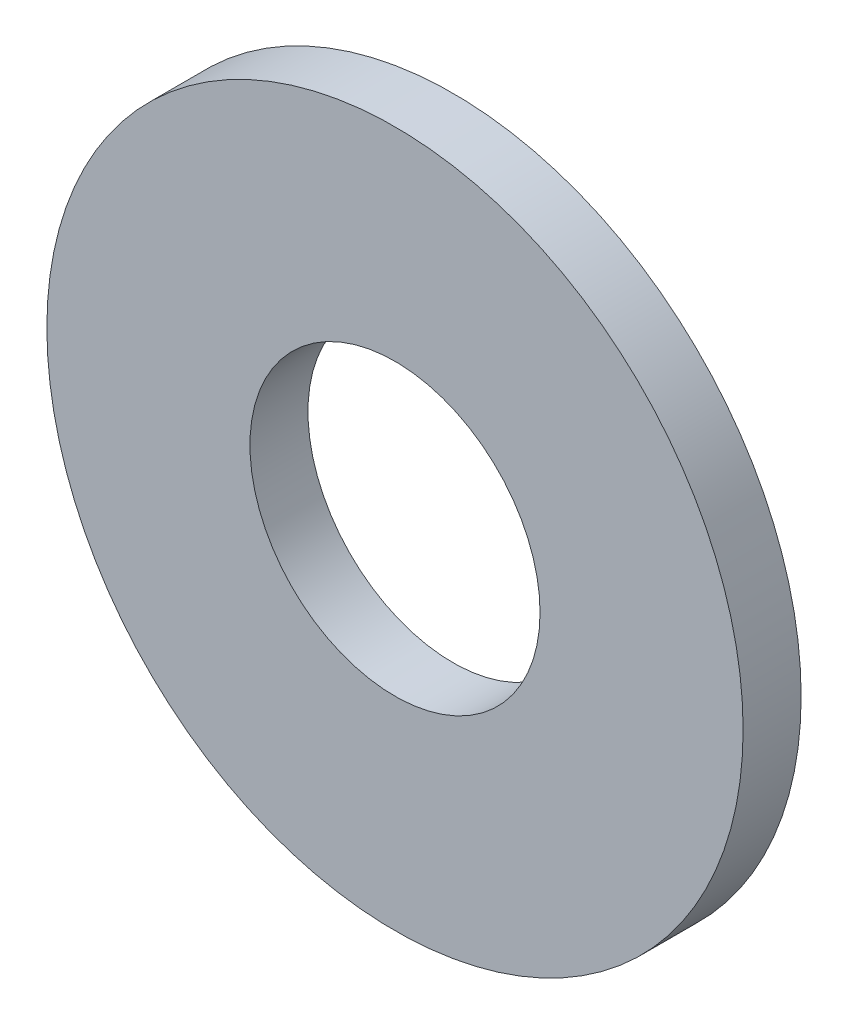
SolidWorks part; units mm, degrees
ref_plane "Front Plane" through (0, 0, 0) normal (0, 0, 1) x (1, 0, 0)
ref_plane "Top Plane" through (0, 0, 0) normal (0, 1, 0) x (1, 0, 0)
ref_plane "Right Plane" through (0, 0, 0) normal (1, 0, 0) x (0, 0, -1)
sketch "Sketch1" plane through (0, 0, 0) normal (0, 0, 1) x (1, 0, 0)
  circle A0 centre (0, 0) radius 3.9688
  circle A1 centre (0, 0) radius 9.525
  dimension "D1" = 7.9375
  dimension "D2" = 19.05
extrude "Boss-Extrude1" add sketch "Sketch1" against normal blind 1.5875
